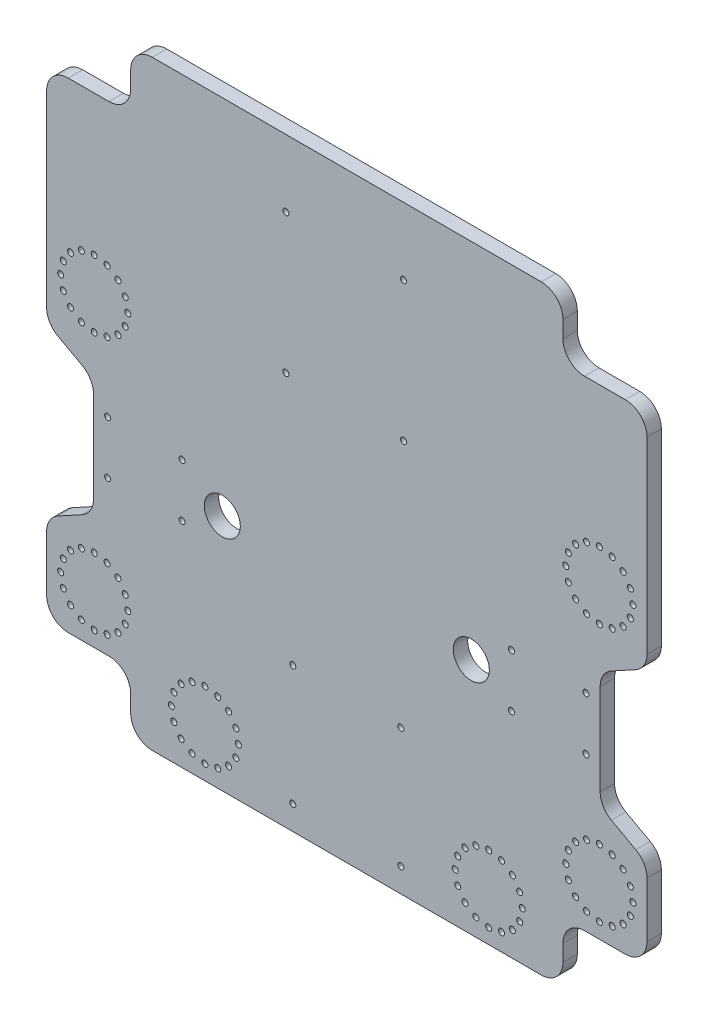
SolidWorks part; units mm, degrees
other "Markup1"
sketch "Sketch7" plane through (25, 0, 0) normal (-0.133, -0.1918, 0.9724) x (0.9904, 0.0125, 0.1379)
material "6061 Alloy"
ref_plane "Front Plane" through (0, 0, 0) normal (0, 0, 1) x (1, 0, 0)
ref_plane "Top Plane" through (0, 0, 0) normal (0, 1, 0) x (1, 0, 0)
ref_plane "Right Plane" through (0, 0, 0) normal (1, 0, 0) x (0, 0, -1)
sketch "Sketch1" plane through (0, 0, 0) normal (0, 0, 1) x (1, 0, 0)
  line L1 (0, 0) -> (300, 0)
  line L2 (0, 0) -> (0, 250)
  line L3 (0, 250) -> (300, 250)
  line L4 (300, 0) -> (300, 250)
  dimension "D1" = 300
  dimension "D2" = 250
extrude "Boss-Extrude1" add sketch "Sketch1" against normal blind 6
sketch "Motor Center Line" plane through (0, 0, -6) normal (0, 0, -1) x (-1, 0, 0)
  line L0 (0, 100) -> (-300, 100) construction
  line L3 (-300, 250) -> (0, 250) construction
  dimension "D1" = 150
sketch "Sketch2" plane through (0, 0, 0) normal (0, 0, 1) x (1, 0, 0)
  line L0 (150, 0.825) -> (150, -0.825) construction
  line L1 (0, 0) -> (20, 0)
  line L2 (0, 0) -> (0, 20)
  line L3 (0, 20) -> (20, 20)
  line L4 (20, 0) -> (20, 20)
  line L5 (300, 20) -> (280, 20)
  line L6 (280, 0) -> (280, 20)
  line L7 (300, 0) -> (280, 0)
  line L8 (300, 0) -> (300, 20)
  line L10 (0, 125) -> (300, 125) construction
  line L11 (0, 250) -> (0, 0) construction
  line L12 (300, 0) -> (300, 250) construction
  line L13 (300, 250) -> (300, 230)
  line L14 (300, 250) -> (280, 250)
  line L15 (280, 250) -> (280, 230)
  line L16 (300, 230) -> (280, 230)
  line L17 (0, 230) -> (20, 230)
  line L18 (20, 250) -> (20, 230)
  line L19 (0, 250) -> (20, 250)
  line L20 (0, 250) -> (0, 230)
  dimension "D1" = 20
sketch "Sketch3" plane through (0, 0, 0) normal (0, 0, 1) x (1, 0, 0)
  line L0 (150, 250) -> (150, 0) construction
  line L1 (0, 0) -> (25, 0)
  line L2 (0, 0) -> (0, 25)
  line L3 (0, 25) -> (25, 25)
  line L4 (25, 0) -> (25, 25)
  line L5 (300, 250) -> (0, 250) construction
  line L6 (0, 0) -> (300, 0) construction
  line L7 (0, 125) -> (300, 125) construction
  line L8 (0, 250) -> (0, 0) construction
  line L9 (300, 0) -> (300, 250) construction
  line L10 (300, 25) -> (275, 25)
  line L11 (275, 0) -> (275, 25)
  line L12 (300, 0) -> (275, 0)
  line L13 (300, 0) -> (300, 25)
  line L14 (300, 250) -> (300, 225)
  line L15 (300, 250) -> (275, 250)
  line L16 (275, 250) -> (275, 225)
  line L17 (300, 225) -> (275, 225)
  line L18 (0, 225) -> (25, 225)
  line L19 (25, 250) -> (25, 225)
  line L20 (0, 250) -> (25, 250)
  line L21 (0, 250) -> (0, 225)
  line L22 (255.5, 73) -> (275, 62.3437)
  line L23 (255.5, 73) -> (255.5, 121.6874)
  line L24 (255.5, 121.6874) -> (275, 132.3437)
  line L25 (275, 132.3437) -> (300, 132.3437)
  line L26 (300, 132.3437) -> (300, 25)
  line L27 (275, 62.3437) -> (275, 25)
  line L28 (44.5, 73) -> (25, 62.3437)
  line L29 (25, 62.3437) -> (25, 25)
  line L30 (44.5, 73) -> (44.5, 121.6874)
  line L31 (265.5, 121.25) -> (265.5, 78.75) construction
  line L32 (44.5, 121.6874) -> (25, 132.3437)
  line L37 (287.5, 132.3437) -> (287.5, 225)
  line L38 (25, 132.3437) -> (0, 132.3437)
  line L39 (12.5, 132.3437) -> (12.5, 225)
  circle A0 centre (201.85, 99.1258) radius 7.5
  circle A1 centre (98.15, 99.1258) radius 7.5
  ellipse E4 centre (201.85, 99.7743) end of major axis (201.2, 99.7743) minor radius 0.6484 construction
  line M15 (0, 250) -> (0, 0)
  line M16 (0, 0) -> (300, 0)
  line M17 (300, 0) -> (300, 250)
  line M18 (300, 250) -> (0, 250)
  dimension "D3" = 15
  dimension "D1" = 25
  dimension "D2" = 10
  dimension "D4" = 70
extrude "Cut-Extrude1" cut sketch "Sketch3" against normal through all both and the other way through all contours L11 L10 M16 M17 | L25 L24 L23 L10 M17 | L17 L16 M17 M18 | L19 L18 M18 M15 | L3 M15 | L4 L3 M16 M15 | A1 | A0 | L18 M15 | L37 L25 L17 M17 region at (12.5, 12.5, 0) region at (19.0279, 84.2975, 0) region at (287.5, 12.5, 0) region at (6.25, 178.6719, 0) region at (280.9721, 84.2975, 0) region at (12.5, 237.5, 0) region at (293.75, 178.6719, 0) region at (287.5, 237.5, 0) region at (201.85, 99.1258, 0) region at (98.15, 99.1258, 0)
sketch "Sketch8" plane through (0, 0, 0) normal (0, 0, 1) x (1, 0, 0)
  circle A0 centre (209.09, 20.16) radius 13.97 construction
  circle A25 centre (209.09, 34.13) radius 1.25
  circle A26 centre (209.09, 6.19) radius 1.25
  circle A27 centre (214.4361, 33.0666) radius 1.25
  circle A28 centre (203.7439, 7.2534) radius 1.25
  circle A29 centre (218.9683, 30.0383) radius 1.25
  circle A30 centre (199.2117, 10.2817) radius 1.25
  circle A31 centre (221.9966, 25.5061) radius 1.25
  circle A32 centre (196.1834, 14.8139) radius 1.25
  circle A33 centre (223.06, 20.16) radius 1.25
  circle A34 centre (195.12, 20.16) radius 1.25
  circle A35 centre (221.9966, 14.8139) radius 1.25
  circle A36 centre (196.1834, 25.5061) radius 1.25
  circle A37 centre (218.9683, 10.2817) radius 1.25
  circle A38 centre (199.2117, 30.0383) radius 1.25
  circle A39 centre (214.4361, 7.2534) radius 1.25
  circle A40 centre (203.7439, 33.0666) radius 1.25
  circle A43 centre (195.12, 20.16) radius 1.6 construction
  circle A44 centre (223.06, 20.16) radius 1.6 construction
  circle A45 centre (90.91, 20.16) radius 13.97 construction
  circle A46 centre (76.94, 20.16) radius 1.25
  circle A47 centre (104.88, 20.16) radius 1.25
  circle A48 centre (76.94, 20.16) radius 1.6 construction
  circle A49 centre (255.1689, 59.2712) radius 1.25
  circle A50 centre (103.8166, 14.8139) radius 1.25
  circle A51 centre (78.0034, 25.5061) radius 1.25
  circle A52 centre (100.7883, 10.2817) radius 1.25
  circle A53 centre (81.0317, 30.0383) radius 1.25
  circle A54 centre (96.2561, 7.2534) radius 1.25
  circle A55 centre (85.5639, 33.0666) radius 1.25
  circle A56 centre (90.91, 6.19) radius 1.25
  circle A57 centre (90.91, 34.13) radius 1.25
  circle A58 centre (85.5639, 7.2534) radius 1.25
  circle A59 centre (96.2561, 33.0666) radius 1.25
  circle A60 centre (81.0317, 10.2817) radius 1.25
  circle A61 centre (100.7883, 30.0383) radius 1.25
  circle A62 centre (78.0034, 14.8139) radius 1.25
  circle A63 centre (103.8166, 25.5061) radius 1.25
  circle A66 centre (104.88, 20.16) radius 1.5 construction
  circle A67 centre (255.1689, 45.3012) radius 13.97 construction
  circle A68 centre (255.1689, 31.3312) radius 1.25
  circle A69 centre (255.1689, 59.2712) radius 1.6 construction
  circle A70 centre (44.8311, 45.3012) radius 13.97 construction
  circle A71 centre (260.515, 58.2078) radius 1.25
  circle A72 centre (249.8228, 32.3946) radius 1.25
  circle A73 centre (265.0472, 55.1795) radius 1.25
  circle A74 centre (245.2907, 35.4229) radius 1.25
  circle A75 centre (268.0755, 50.6473) radius 1.25
  circle A76 centre (242.2623, 39.9551) radius 1.25
  circle A77 centre (269.1389, 45.3012) radius 1.25
  circle A78 centre (241.1989, 45.3012) radius 1.25
  circle A79 centre (268.0755, 39.9551) radius 1.25
  circle A80 centre (242.2623, 50.6473) radius 1.25
  circle A81 centre (265.0472, 35.4229) radius 1.25
  circle A82 centre (245.2907, 55.1795) radius 1.25
  circle A83 centre (260.515, 32.3946) radius 1.25
  circle A84 centre (249.8228, 58.2078) radius 1.25
  circle A87 centre (44.8311, 59.2712) radius 1.25
  circle A88 centre (44.8311, 31.3312) radius 1.25
  circle A89 centre (50.1772, 58.2078) radius 1.25
  circle A90 centre (39.485, 32.3946) radius 1.25
  circle A91 centre (54.7093, 55.1795) radius 1.25
  circle A92 centre (34.9528, 35.4229) radius 1.25
  circle A93 centre (57.7377, 50.6473) radius 1.25
  circle A94 centre (31.9245, 39.9551) radius 1.25
  circle A95 centre (58.8011, 45.3012) radius 1.25
  circle A96 centre (30.8611, 45.3012) radius 1.25
  circle A97 centre (57.7377, 39.9551) radius 1.25
  circle A98 centre (31.9245, 50.6473) radius 1.25
  circle A99 centre (54.7093, 35.4229) radius 1.25
  circle A100 centre (34.9528, 55.1795) radius 1.25
  circle A101 centre (50.1772, 32.3946) radius 1.25
  circle A102 centre (39.485, 58.2078) radius 1.25
  circle A105 centre (44.8311, 31.3312) radius 1.5 construction
  circle A106 centre (44.8311, 59.2712) radius 1.5 construction
  circle A107 centre (255.1689, 152.6711) radius 13.97 construction
  circle A108 centre (255.1689, 166.6411) radius 1.25
  circle A109 centre (255.1689, 138.7011) radius 1.25
  circle A110 centre (249.8228, 139.7645) radius 1.25
  circle A111 centre (260.515, 165.5777) radius 1.25
  circle A112 centre (245.2907, 142.7929) radius 1.25
  circle A113 centre (265.0472, 162.5494) radius 1.25
  circle A114 centre (242.2623, 147.3251) radius 1.25
  circle A115 centre (268.0755, 158.0172) radius 1.25
  circle A116 centre (241.1989, 152.6711) radius 1.25
  circle A117 centre (269.1389, 152.6711) radius 1.25
  circle A118 centre (242.2623, 158.0172) radius 1.25
  circle A119 centre (268.0755, 147.3251) radius 1.25
  circle A120 centre (245.2907, 162.5494) radius 1.25
  circle A121 centre (265.0472, 142.7929) radius 1.25
  circle A122 centre (249.8228, 165.5777) radius 1.25
  circle A123 centre (260.515, 139.7645) radius 1.25
  circle A124 centre (255.1689, 166.6411) radius 1.6 construction
  circle A125 centre (255.1689, 138.7011) radius 1.5 construction
  circle A128 centre (44.8311, 152.6711) radius 13.97 construction
  circle A129 centre (44.8311, 166.6411) radius 1.25
  circle A130 centre (44.8311, 138.7011) radius 1.25
  circle A131 centre (39.485, 139.7645) radius 1.25
  circle A132 centre (50.1772, 165.5777) radius 1.25
  circle A133 centre (34.9528, 142.7929) radius 1.25
  circle A134 centre (54.7093, 162.5494) radius 1.25
  circle A135 centre (31.9245, 147.3251) radius 1.25
  circle A136 centre (57.7377, 158.0172) radius 1.25
  circle A137 centre (30.8611, 152.6711) radius 1.25
  circle A138 centre (58.8011, 152.6711) radius 1.25
  circle A139 centre (31.9245, 158.0172) radius 1.25
  circle A140 centre (57.7377, 147.3251) radius 1.25
  circle A141 centre (34.9528, 162.5494) radius 1.25
  circle A142 centre (54.7093, 142.7929) radius 1.25
  circle A143 centre (39.485, 165.5777) radius 1.25
  circle A144 centre (50.1772, 139.7645) radius 1.25
  circle A147 centre (44.8311, 166.6411) radius 1.6 construction
  circle A148 centre (44.8311, 138.7011) radius 1.6 construction
  point P40 (209.09, 20.16)
  point P87 (90.91, 20.16)
  point P129 (255.1689, 45.3012)
  point P167 (44.8311, 45.3012)
  point P192 (255.1689, 152.6711)
  point P194 (0, 0)
  point P197 (64.2942, 168.5007)
  point P234 (44.8311, 152.6711)
  point P235 (64.1831, 183.692)
  point P236 (64.0129, 182.0751)
  point P237 (56.1507, 161.3937)
  dimension "D1" = 2.5
  dimension "D2" = 2.5
  dimension "D5" = 2.5
  dimension "D7" = 2.5
  dimension "D9" = 5.4508
  dimension "D10" = 5.3461
  dimension "D11" = 5.3461
  dimension "D12" = 2.5
  dimension "D15" = 2.5
  dimension "D14" = 5.4508
  dimension "D17" = 5.4508
  dimension "D3" = 8
  dimension "D4" = 8
  dimension "D6" = 8
  dimension "D8" = 8
  dimension "D13" = 8
  dimension "D16" = 8
sketch "Sketch4" plane through (0, 0, 0) normal (0, 0, 1) x (1, 0, 0)
  arc A0 (174.9953, 164.0221) -> (172.2953, 164.0221) centre (173.6453, 164.0221) ccw construction
  arc A1 (125.9953, 164.0221) -> (123.2953, 164.0221) centre (124.6453, 164.0221) ccw construction
  arc A4 (125.9953, 222.0221) -> (123.2953, 222.0221) centre (124.6453, 222.0221) ccw construction
  arc A5 (174.9953, 222.0221) -> (172.2953, 222.0221) centre (173.6453, 222.0221) ccw construction
  point P23 (127.5, 10)
  point P25 (172.5, 10)
  point P27 (127.5, 60)
  point P29 (172.5, 60)
  point P31 (124.6453, 164.0221)
  point P33 (173.6453, 164.0221)
  point P35 (124.6453, 222.0221)
  point P37 (173.6453, 222.0221)
  point P39 (218.6, 111)
  point P41 (249.6, 111)
  point P43 (249.6, 89)
  point P45 (218.6, 89)
  point P47 (81.4, 89.0063)
  point P49 (50.4, 89.0063)
  point P51 (81.4, 111.0063)
  point P53 (50.4, 111.0063)
extrude "Cut-Extrude4" cut sketch "Sketch8" against normal through all
sketch "Sketch6" plane through (0, 0, 0) normal (0, 0, 1) x (1, 0, 0)
  line L0 (287.5, 225) -> (275, 225)
  line L1 (275, 0) -> (240, 0)
  line L2 (275, 0) -> (275, 25)
  line L3 (275, 25) -> (240, 25)
  line L4 (240, 0) -> (240, 25)
  line L5 (240, 25) -> (255.5, 73)
  line L6 (150, 250) -> (150, 0) construction
  line L7 (275, 250) -> (25, 250) construction
  line L8 (25, 0) -> (275, 0) construction
  line L9 (60, 25) -> (44.5, 73)
  line L10 (25, 25) -> (60, 25)
  line L11 (60, 0) -> (60, 25)
  line L12 (25, 0) -> (60, 0)
  line L13 (25, 0) -> (25, 25)
  line L14 (275, 250) -> (240, 250)
  line L15 (25, 225) -> (60, 225)
  line L16 (25, 225) -> (25, 250)
  line L17 (25, 250) -> (60, 250)
  line L18 (60, 225) -> (60, 250)
  line L19 (240, 225) -> (240, 250)
  line L20 (275, 225) -> (240, 225)
  line L21 (275, 225) -> (275, 250)
  line L22 (25, 225) -> (25, 132.3437)
  line L23 (275, 132.3437) -> (275, 225)
  line L24 (287.5, 225) -> (287.5, 132.3437)
  line L25 (287.5, 132.3437) -> (275, 132.3437)
  line L26 (25, 225) -> (12.5, 225)
  line L27 (12.5, 225) -> (12.5, 132.3437)
  line L28 (12.5, 132.3437) -> (25, 132.3437)
  dimension "D1" = 25
  dimension "D2" = 35
extrude "Cut-Extrude3" cut sketch "Sketch6" against normal through all contours L11 L10 | L10 L9 | L4 L3 | L5 L3 | L15 L18 | L20 L19 | L22 | L23 region at (281.25, 178.6719, 0) region at (257.5, 237.5, 0) region at (257.5, 12.5, 0) region at (42.5, 12.5, 0) region at (42.5, 237.5, 0) region at (18.75, 178.6719, 0)
sketch "Sketch5" plane through (0, 0, 0) normal (0, 0, 1) x (1, 0, 0)
  circle A0 centre (50.4, 89.0063) radius 1.25
  point P3 (0, 0)
  point P4 (50.4, 89.0063)
  point P5 (59.3996, 88.3596)
  point P6 (50.4, 89.0063)
  dimension "D1" = 2.5
extrude "Cut-Extrude2" cut sketch "Sketch5" against normal through all both
pattern_sketch "Sketch-Pattern1" of "Cut-Extrude2" driven by "Sketch4"
fillet "Fillet1" radius 9 20 edges at (255.5, 121.6874, -3) (44.5, 121.6874, -3) (44.5, 73, -3) (25, 62.3437, -3) (255.5, 73, -3) (275, 62.3437, -3) (240, 250, -3) (240, 225, -3) (60, 250, -3) (60, 225, -3) (60, 0, -3) (240, 0, -3) (275, 225, -3) (275, 132.3437, -3) (25, 225, -3) (25, 132.3437, -3) (60, 25, -3) (25, 25, -3) (275, 25, -3) (240, 25, -3)
